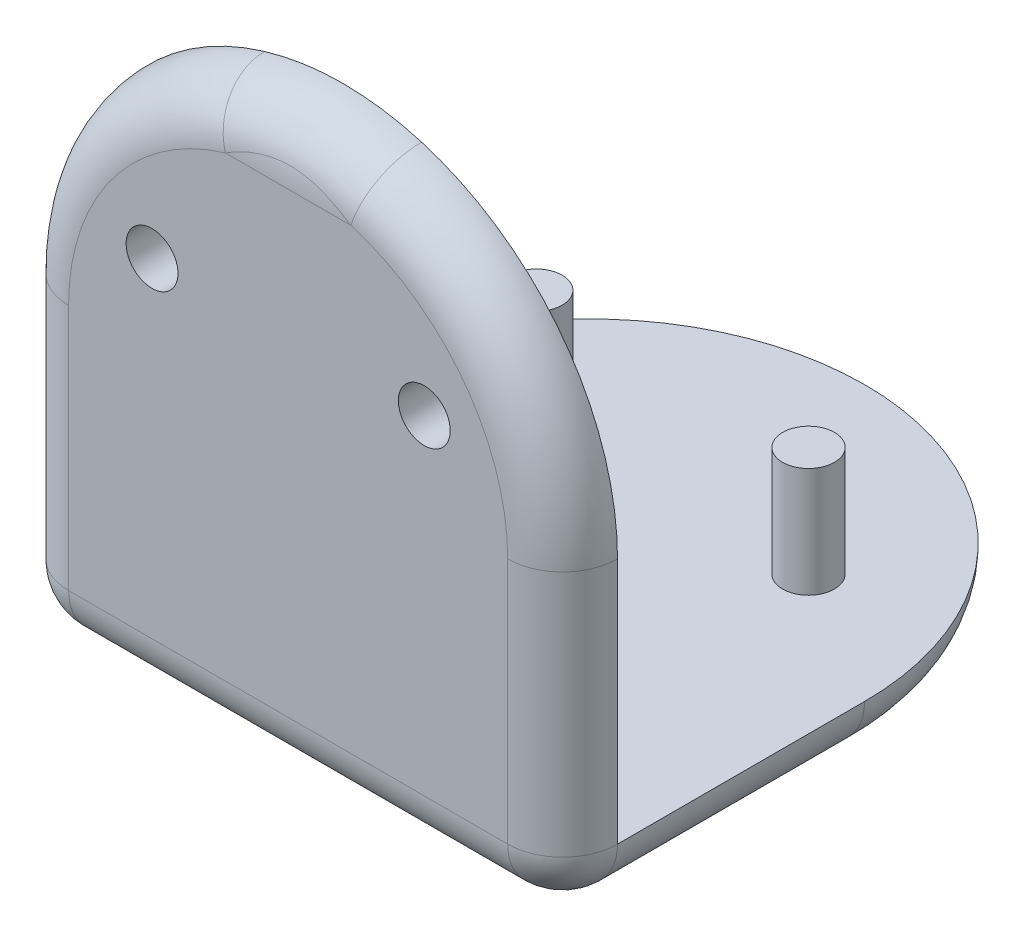
SolidWorks part; units mm, degrees
ref_plane "Front Plane" through (0, 0, 0) normal (0, 0, 1) x (1, 0, 0)
ref_plane "Top Plane" through (0, 0, 0) normal (0, 1, 0) x (1, 0, 0)
ref_plane "Right Plane" through (0, 0, 0) normal (1, 0, 0) x (0, 0, -1)
sketch "Sketch1" plane through (0, 0, 0) normal (1, 0, 0) x (0, 0, -1)
  line L0 (-3.175, 31.75) -> (-3.175, -3.175)
  line L1 (-3.175, -3.175) -> (31.75, -3.175)
  line L2 (31.75, -3.175) -> (31.75, 0)
  line L3 (31.75, 0) -> (0, 0)
  line L4 (0, 0) -> (0, 31.75)
  line L5 (0, 31.75) -> (-3.175, 31.75)
  dimension "D1" = 3.175
  dimension "D2" = 3.175
  dimension "D3" = 31.75
  dimension "D4" = 31.75
extrude "Boss-Extrude1" add sketch "Sketch1" along normal blind 31.75
fillet "Fillet1" radius 6 2 edges at (15.875, 31.75, 3.175) (15.875, -3.175, -31.75)
sketch "Sketch2" plane through (0, 0, 3.175) normal (0, 0, 1) x (1, 0, 0)
  line L0 (8.001, 19.05) -> (23.749, 19.05) construction
  line L1 (31.75, -3.175) -> (0, -3.175) construction
  line L2 (31.75, 26.4567) -> (31.75, -3.175) construction
  line L3 (15.875, 31.75) -> (15.875, -3.175) construction
  line L4 (0, 26.4567) -> (0, -3.175) construction
  line L5 (31.75, 31.75) -> (0, 31.75) construction
  line L7 (0, 14.2875) -> (0, 31.75)
  line L8 (0, 31.75) -> (31.75, 31.75)
  line L9 (31.75, 31.75) -> (31.75, 14.2875)
  circle A0 centre (8.001, 19.05) radius 1.5
  circle A1 centre (23.749, 19.05) radius 1.5
  arc A2 (31.75, 14.2875) -> (0, 14.2875) centre (15.875, 14.2875) ccw
  point P4 (15.875, 19.05)
  point P7 (15.875, -3.175)
  point P9 (15.875, 14.2875)
  dimension "D1" = 3
  dimension "D2" = 15.748
  dimension "D3" = 19.05
extrude "Cut-Extrude1" cut sketch "Sketch2" against normal through all
sketch "Sketch3" plane through (0, -3.175, 0) normal (0, -1, 0) x (1, 0, 0)
  line L0 (8.001, -19.05) -> (23.749, -19.05) construction
  line L1 (31.75, 3.175) -> (0, 3.175) construction
  line L2 (15.875, -31.75) -> (15.875, 3.175) construction
  line L4 (31.75, -31.75) -> (0, -31.75) construction
  line L5 (31.75, 3.175) -> (31.75, -26.4567) construction
  line L6 (31.75, -31.75) -> (31.75, -14.2875)
  line L7 (31.75, -31.75) -> (0, -31.75)
  line L8 (0, -31.75) -> (0, -14.2875)
  circle A0 centre (8.001, -19.05) radius 1.5
  circle A1 centre (23.749, -19.05) radius 1.5
  arc A2 (0, -14.2875) -> (31.75, -14.2875) centre (15.875, -14.2875) ccw
  point P4 (15.875, -19.05)
  point P18 (15.875, 3.175)
  line M3 (0, 3.175) -> (0, -26.4567)
  line M4 (0, -26.4567) -> (31.75, -26.4567)
  line M5 (31.75, -26.4567) -> (31.75, 3.175)
  dimension "D1" = 3
  dimension "D2" = 15.748
  dimension "D3" = 19.05
extrude "Cut-Extrude2" cut sketch "Sketch3" against normal through all contours A2 L8 L7 L6 M4 | A2 M4 M5 | A2 M3 M4 region at (15.875, -3.175, -31.4281) region at (30.1148, -3.175, -23.534) region at (1.6352, -3.175, -23.534)
fillet "Fillet2" radius 3.175 1 edges at (15.875, -3.175, 3.175)
fillet "Fillet3" radius 3.175 12 edges at (13.5464, -2.0237, -29.9908) (30.2599, -3.175, -21.0024) (31.75, -3.175, -7.1438) (31.75, -2.2451, 2.2451) (31.75, 7.1437, 3.175) (30.2599, 21.0024, 3.175) (13.5464, 29.9908, 2.0237) (1.4901, 21.0024, 3.175) (0, 7.1437, 3.175) (0, -2.2451, 2.2451) (0, -3.175, -7.1438) (1.4901, -3.175, -21.0024)
extrude "Boss-Extrude2" add sketch "Sketch3<3>" against normal blind 9.525 contours A1 | A0 region at (8.001, -3.175, -19.05) region at (23.749, -3.175, -19.05)
sketch "Sketch3<3>" plane through (0, -3.175, 0) normal (0, -1, 0) x (1, 0, 0) same geometry as "Sketch3"
